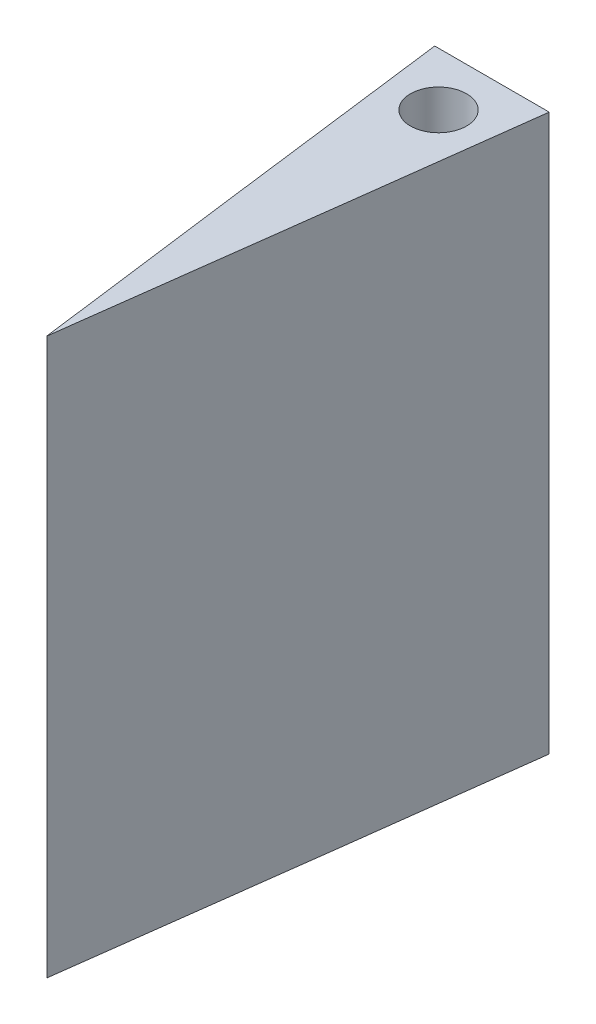
SolidWorks part; units mm, degrees
ref_plane "Front Plane" through (0, 0, 0) normal (0, 0, 1) x (1, 0, 0)
ref_plane "Top Plane" through (0, 0, 0) normal (0, 1, 0) x (1, 0, 0)
ref_plane "Right Plane" through (0, 0, 0) normal (1, 0, 0) x (0, 0, -1)
sketch "Sketch1" plane through (0, 0, 0) normal (0, 1, 0) x (1, 0, 0)
  line L0 (1.1081, 1.7265) -> (-45.0799, 1.7265) construction
  line L1 (-45.0799, 1.7265) -> (-45.0799, -11.2275) construction
  line L2 (-45.0799, -11.2275) -> (43.7517, -11.2275) construction
  line L3 (1.1081, 103.3269) -> (1.1081, -99.8738) construction
  line L4 (-45.0799, -11.2275) -> (-45.0799, -20.7525) construction
  line L5 (-28.2049, 1.7265) -> (-28.2049, -3.6075) construction
  line L6 (-9.9553, -3.6075) -> (-6.7697, -3.6075)
  line L7 (-28.2049, -3.6075) -> (-9.9553, -3.6075) construction
  line L8 (-6.7697, -3.6075) -> (1.1081, -3.6075) construction
  line L9 (8.9859, -3.6075) -> (12.1715, -3.6075)
  line L10 (12.1715, -3.6075) -> (18.1346, -3.6075) construction
  line L11 (12.1715, -3.6075) -> (18.1346, -3.6075) construction
  line L12 (18.1346, -3.6075) -> (29.3788, -3.6075) construction
  line L13 (1.1081, -3.6075) -> (8.9859, -3.6075) construction
  line L14 (-6.7697, -3.6075) -> (8.9859, -3.6075)
  circle A0 centre (1.1081, -11.3265) radius 1.9844 construction
  circle A1 centre (1.1081, -11.3265) radius 1.9844
  spline S0 degree 3 poles (1.1081, -99.8738) (4.5273, -73.5318) (7.9866, -47.1872) (10.6029, -20.7525) knots 0 0 0 0 0.38497 0.38497 0.38497 0.38497
  spline S3 degree 3 poles (1.1081, -99.8738) (-2.3112, -73.5318) (-5.7704, -47.1872) (-8.3867, -20.7525) knots 0 0 0 0 0.38497 0.38497 0.38497 0.38497
  spline S4 degree 3 poles (10.6029, -20.7525) (11.1, -15.7302) (11.6306, -10.016) (12.114, -4.2968) (12.1715, -3.6075) knots 0.38497 0.38497 0.38497 0.38497 0.458109 0.468132 0.468132 0.468132 0.468132
  spline S5 degree 3 poles (-8.3867, -20.7525) (-8.8838, -15.7302) (-9.4144, -10.016) (-9.8978, -4.2968) (-9.9553, -3.6075) knots 0.38497 0.38497 0.38497 0.38497 0.458109 0.468132 0.468132 0.468132 0.468132
  spline S8 degree 3 poles (12.1715, -3.6075) (12.8364, 4.367) (14.1908, 23.6726) (14.0058, 48.0803) (13.0188, 67.5796) (11.3266, 78.9472) (9.5869, 86.9693) (8.1237, 93.6397) (6.4505, 97.563) (4.8164, 101.3994) (2.3437, 102.5279) (1.1081, 103.3269) knots 0.468132 0.468132 0.468132 0.468132 0.584075 0.748482 0.821537 0.866809 0.914778 0.94069 0.965303 0.976863 1 1 1 1 construction
  spline S9 degree 3 poles (1.1081, 99.6196) (1.2739, 99.518) (1.6209, 99.2976) (2.0134, 99.0137) (2.3095, 98.7539) (2.4667, 98.5788) (2.6076, 98.3713) (2.8163, 97.9774) (3.0534, 97.4394) (3.4327, 96.5453) (3.8774, 95.496) (4.541, 93.8448) (5.2023, 91.9048) (5.8236, 89.3366) (6.4213, 86.5662) (7.0145, 83.8293) (7.767, 80.1951) (8.6007, 75.6781) (9.6391, 68.4081) (10.3034, 59.2354) (10.6788, 47.9926) (10.8555, 36.7918) (10.7415, 25.5951) (10.3009, 14.4244) (9.6564, 4.6878) (9.1767, -1.3266) (8.9859, -3.6075) knots 0.118744 0.118744 0.118744 0.118744 0.122149 0.125554 0.12896 0.132365 0.13577 0.139175 0.142581 0.145986 0.152796 0.159607 0.173228 0.186849 0.20047 0.214091 0.227711 0.254953 0.282195 0.336679 0.391163 0.445646 0.50013 0.554614 0.609098 0.642376 0.642376 0.642376 0.642376 construction
  spline S10 degree 3 poles (-7.1984, 1.7265) (-7.237, 2.2289) (-7.5577, 6.4638) (-8.0847, 14.4244) (-8.5253, 25.5951) (-8.6393, 36.7918) (-8.4626, 47.9926) (-8.0872, 59.2354) (-7.4229, 68.4081) (-6.3845, 75.6781) (-5.5508, 80.1951) (-4.7983, 83.8293) (-4.2051, 86.5662) (-3.6074, 89.3366) (-2.9861, 91.9048) (-2.3248, 93.8448) (-1.6612, 95.496) (-1.2165, 96.5453) (-0.8372, 97.4394) (-0.6001, 97.9774) (-0.3914, 98.3713) (-0.2505, 98.5788) (-0.0933, 98.7539) (0.2028, 99.0137) (0.5953, 99.2976) (0.9423, 99.518) (1.1081, 99.6196) knots 0.492798 0.492798 0.492798 0.492798 0.50013 0.554614 0.609098 0.663581 0.718065 0.772549 0.827033 0.854275 0.881516 0.895137 0.908758 0.922379 0.936 0.949621 0.956432 0.963242 0.966647 0.970053 0.973458 0.976863 0.980268 0.983674 0.987079 0.990484 0.990484 0.990484 0.990484 construction
  spline S11 degree 3 poles (-10.3826, 1.7265) (-10.8572, 7.9268) (-11.9611, 25.4575) (-11.7896, 48.0803) (-10.8026, 67.5796) (-9.1104, 78.9472) (-7.3707, 86.9693) (-5.9075, 93.6397) (-4.2343, 97.563) (-2.6002, 101.3994) (-0.1276, 102.5279) (1.1081, 103.3269) knots 0.493976 0.493976 0.493976 0.493976 0.584075 0.748482 0.821537 0.866809 0.914778 0.94069 0.965303 0.976863 1 1 1 1 construction
  spline S12 degree 3 poles (-9.9553, -3.6075) (-10.1035, -1.8299) (-10.2465, -0.0519) (-10.3826, 1.7265) knots 0.468132 0.468132 0.468132 0.468132 0.493976 0.493976 0.493976 0.493976 construction
  spline S13 degree 3 poles (-6.7697, -3.6075) (-6.9185, -1.8292) (-7.0618, -0.0511) (-7.1984, 1.7265) knots 0.466852 0.466852 0.466852 0.466852 0.492798 0.492798 0.492798 0.492798 construction
  dimension "D4" = 3.9688
  dimension "D1" = 12.954
  dimension "D2" = 9.525
  dimension "D3" = 5.334
extrude "Boss-Extrude1" add sketch "Sketch1" along normal blind 169.8727
sketch "Sketch2" plane through (0, 169.8727, 0) normal (0, 1, 0) x (1, 0, 0)
  line L1 (-9.9553, -3.6075) -> (25.8085, -3.6075)
  line L2 (-9.9553, -3.6075) -> (-9.9553, -26.3125)
  line L3 (-9.9553, -26.3125) -> (25.8085, -26.3125)
  line L4 (25.8085, -3.6075) -> (25.8085, -26.3125)
  circle A0 centre (1.1081, -11.3265) radius 1.9844 construction
  dimension "D1" = 14.986
extrude "Cut-Extrude1" cut sketch "Sketch2" against normal blind 23.0581
extrude "Cut-Extrude2" cut sketch "Sketch2<2>" along normal blind 23.0581 from surface starting at face at (-1.1046, 0, 29.7187)
sketch "Sketch2<2>" plane through (0, 169.8727, 0) normal (0, 1, 0) x (1, 0, 0) same geometry as "Sketch2"
fillet "Fillet1" radius 7.62 6 edges at (-7.8242, 11.5291, 26.3125) (10.0403, 11.5291, 26.3125) (12.1715, 84.9363, 3.6075) (-7.8242, 158.3436, 26.3125) (10.0403, 158.3436, 26.3125)
sketch "Sketch6" plane through (0, 0, 0) normal (0, -1, 0) x (1, 0, 0)
  line L0 (1.1081, 3.6075) -> (1.1081, 99.8738) construction
  line L1 (-1.6395, 3.6075) -> (3.8557, 3.6075) construction
  line L2 (-6.9254, 34.7606) -> (9.1416, 34.7606) construction
  circle A0 centre (1.1081, 71.9338) radius 2
  circle A1 centre (1.1081, 34.7606) radius 2
  dimension "D1" = 4
  dimension "D2" = 27.94
extrude "Cut-Extrude3" cut sketch "Sketch6" against normal through all both and the other way through all
sketch "Sketch7" plane through (0, 0, 0) normal (1, 0, 0) x (0, 0, -1)
  line L0 (-3.6075, 146.8145) -> (-3.6075, 23.0581) construction
  line L1 (-99.8738, 0) -> (-3.6075, 0)
  line L2 (-99.8738, 0) -> (-99.8738, 79.911)
  line L3 (-99.8738, 79.911) -> (-3.6075, 79.911)
  line L4 (-3.6075, 0) -> (-3.6075, 79.911)
  line L6 (-99.8738, 169.8727) -> (-3.6075, 169.8727)
  line L7 (-99.8738, 169.8727) -> (-99.8738, 119.5579)
  line L8 (-99.8738, 119.5579) -> (-3.6075, 119.5579)
  line L9 (-3.6075, 169.8727) -> (-3.6075, 119.5579)
  dimension "D2" = 39.6469
extrude "Cut-Extrude4" cut sketch "Sketch7" against normal through all both and the other way through all
sketch "Sketch8" plane through (0, 79.911, 0) normal (0, -1, 0) x (1, 0, 0)
  line L1 (-35.7382, 68.1238) -> (19.5961, 68.1238)
  line L2 (-35.7382, 68.1238) -> (-35.7382, -22.5784)
  line L3 (-35.7382, -22.5784) -> (19.5961, -22.5784)
  line L4 (19.5961, 68.1238) -> (19.5961, -22.5784)
  dimension "D2" = 31.75
extrude "Cut-Extrude5" cut sketch "Sketch8" against normal through all both
